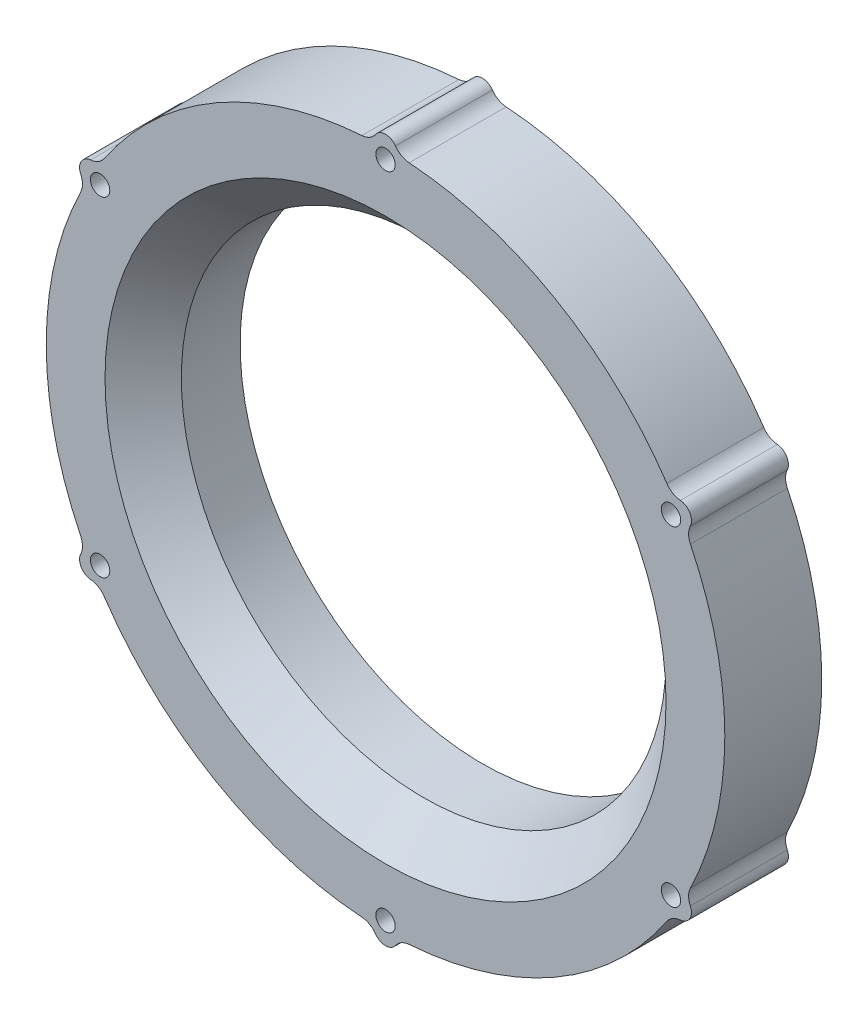
SolidWorks part; units mm, degrees
material "6061-T6 (SS)"
ref_plane "Front Plane" through (0, 0, 0) normal (0, 0, 1) x (1, 0, 0)
ref_plane "Top Plane" through (0, 0, 0) normal (0, 1, 0) x (1, 0, 0)
ref_plane "Right Plane" through (0, 0, 0) normal (1, 0, 0) x (0, 0, -1)
sketch "Sketch1" plane through (0, 0, 0) normal (0, 0, 1) x (1, 0, 0)
  line L0 (0, 0) -> (88.9, 0) construction
  line L1 (0, 0) -> (76.9897, 44.45) construction
  line L2 (0, 0) -> (76.9897, -44.45) construction
  line L3 (0, 0) -> (0, -88.9) construction
  line L4 (0, 0) -> (-76.9897, -44.45) construction
  line L5 (0, 0) -> (-76.9897, 44.45) construction
  line L6 (0, 0) -> (0, 88.9) construction
  circle A0 centre (0, 0) radius 88.9
  circle A1 centre (0, 0) radius 63.5
  circle A2 centre (76.9897, 44.45) radius 3.175
  circle A3 centre (76.9897, -44.45) radius 3.175
  circle A4 centre (0, -88.9) radius 3.175
  circle A5 centre (-76.9897, -44.45) radius 3.175
  circle A6 centre (-76.9897, 44.45) radius 3.175
  circle A7 centre (0, 88.9) radius 3.175
  point P14 (0, 0)
  point P20 (0, 0)
  dimension "D1" = 177.8
  dimension "D2" = 127
  dimension "D5" = 6.35
  dimension "D3" = 30
  dimension "D4" = 6
extrude "Boss-Extrude1" add sketch "Sketch1" along normal blind 25.4 contours A7 A0 A6 A5 A4 A3 A2 A1 | A0 A7 | A0 A7 | A0 A2 | A0 A2 | A0 A3 | A0 A3 | A0 A4 | A0 A4 | A0 A5 | A0 A5 | A0 A6 | A0 A6 region at (83.8287, -20.8648, 0) region at (75.8139, 43.7712, 0) region at (78.1477, 45.1186, 0) region at (78.1477, -45.1186, 0) region at (75.8139, -43.7712, 0) region at (0, 87.5423, 0) region at (0, 90.2372, 0) region at (0, -90.2372, 0) region at (0, -87.5423, 0) region at (-75.8139, 43.7712, 0) region at (-78.1477, 45.1186, 0) region at (-78.1477, -45.1186, 0) region at (-75.8139, -43.7712, 0)
chamfer "Chamfer1" distance 10 angle 45 1 edges at (63.5, 0, 25.4)
sketch "Sketch3" plane through (0, 0, 25.4) normal (0, 0, 1) x (1, 0, 0)
  line L0 (0, 0) -> (74.79, 43.18) construction
  line L1 (0, 0) -> (86.36, 0) construction
  circle A7 centre (0, 0) radius 86.36
  circle A8 centre (74.79, 43.18) radius 2.54
  circle A9 centre (74.79, -43.18) radius 2.54
  circle A10 centre (0, -86.36) radius 2.54
  circle A11 centre (-74.79, -43.18) radius 2.54
  circle A12 centre (-74.79, 43.18) radius 2.54
  circle A13 centre (0, 86.36) radius 2.54
  point P15 (0, 0)
  point P20 (0, 0)
  dimension "D1" = 172.72
  dimension "D3" = 5.08
  dimension "D2" = 30
  dimension "D4" = 6
extrude "Cut-Extrude1" cut sketch "Sketch3" against normal through all contours A7 A8 | A7 A8 | A7 A13 | A7 A13 | A7 A12 | A7 A12 | A7 A10 | A7 A10 | A7 A9 | A7 A9 | A11 region at (73.8506, 42.6376, 25.4) region at (75.7177, 43.7156, 25.4) region at (75.7177, -43.7156, 25.4) region at (73.8506, -42.6376, 25.4) region at (0, 85.2753, 25.4) region at (0, 87.4313, 25.4) region at (0, -87.4313, 25.4) region at (0, -85.2753, 25.4) region at (-73.8506, 42.6376, 25.4) region at (-75.7177, 43.7156, 25.4)
fillet "Fillet1" radius 4.7625 12 edges at (75.3533, 47.1708, 12.7) (78.5278, 41.6725, 12.7) (78.5278, -41.6725, 12.7) (75.3533, -47.1708, 12.7) (3.1745, -88.8433, 12.7) (-3.1745, -88.8433, 12.7) (-75.3533, -47.1708, 12.7) (-78.5278, -41.6725, 12.7) (-78.5278, 41.6725, 12.7) (-75.3533, 47.1708, 12.7) (-3.1745, 88.8433, 12.7) (3.1745, 88.8433, 12.7)
